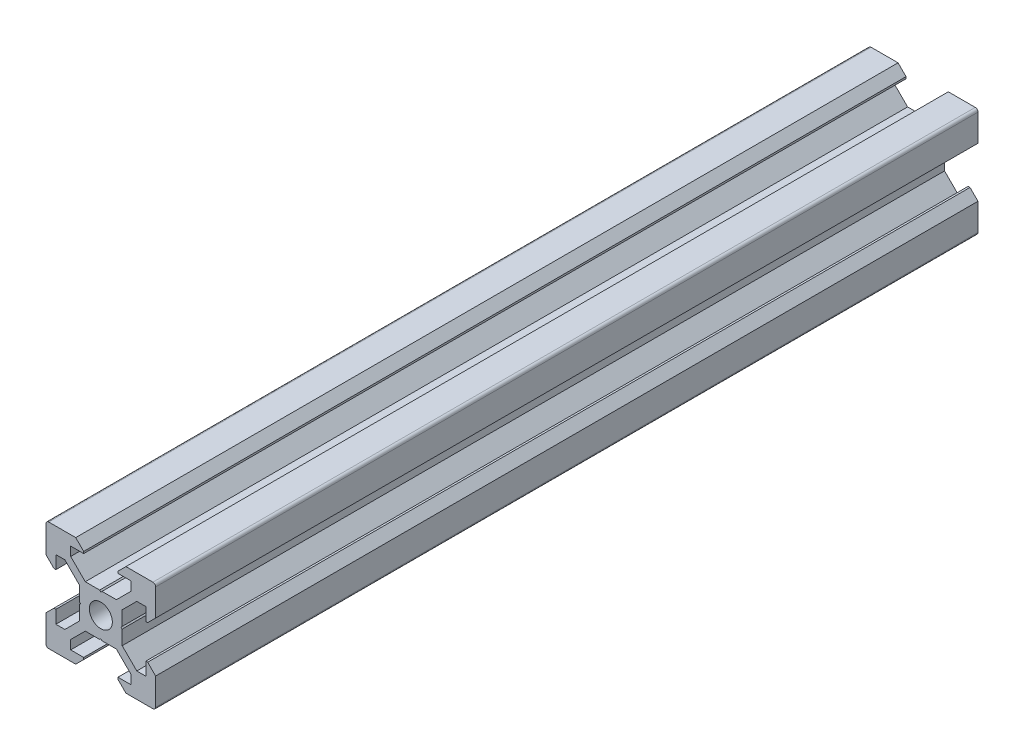
SolidWorks part; units mm, degrees
material "6061-T6 (SS)"
ref_plane "Front Plane" through (0, 0, 0) normal (0, 0, 1) x (1, 0, 0)
ref_plane "Top Plane" through (0, 0, 0) normal (0, 1, 0) x (1, 0, 0)
ref_plane "Right Plane" through (0, 0, 0) normal (1, 0, 0) x (0, 0, -1)
sketch "Sketch1" plane through (0, 0, 0) normal (0, 0, 1) x (1, 0, 0)
  line L1 (9.5, -10) -> (-9.5, -10)
  line L2 (10, -9.5) -> (10, 9.5)
  line L3 (9.5, 10) -> (-9.5, 10)
  line L4 (-10, -9.5) -> (-10, 9.5)
  line L5 (10, -10) -> (-10, 10) construction
  line L6 (10, 10) -> (-10, -10) construction
  circle A0 centre (0, 0) radius 2.1
  arc A1 (-9.5, 10) -> (-10, 9.5) centre (-9.5, 9.5) ccw
  arc A2 (10, 9.5) -> (9.5, 10) centre (9.5, 9.5) ccw
  arc A3 (9.5, -10) -> (10, -9.5) centre (9.5, -9.5) ccw
  arc A4 (-9.5, -10) -> (-10, -9.5) centre (-9.5, -9.5) cw
  point P0 (0, 0)
  line B0 (0, 0) -> (0, 10) construction
  line B1 (0, 3.69) -> (-0.21, 3.9)
  line B2 (-0.21, 3.9) -> (-2.8393, 3.9)
  line B3 (-2.8393, 3.9) -> (-5.5, 6.5607)
  line B4 (-5.5, 6.5607) -> (-5.5, 8.2)
  line B5 (-5.5, 8.2) -> (-3.125, 8.2)
  line B6 (-3.125, 8.2) -> (-3.125, 8.545)
  line B7 (-3.125, 8.545) -> (-4.58, 10)
  line B8 (-4.58, 10) -> (4.58, 10)
  line B9 (0, 0) -> (-5.9132, 5.9132) construction
  line B10 (3.125, 8.545) -> (4.58, 10)
  line B11 (3.125, 8.2) -> (3.125, 8.545)
  line B12 (5.5, 8.2) -> (3.125, 8.2)
  line B13 (5.5, 6.5607) -> (5.5, 8.2)
  line B14 (2.8393, 3.9) -> (5.5, 6.5607)
  line B15 (0.21, 3.9) -> (2.8393, 3.9)
  line B16 (0, 3.69) -> (0.21, 3.9)
  line B17 (0, 0) -> (-10, 0) construction
  line B18 (-3.69, 0) -> (-3.9, -0.21)
  line B19 (-3.9, -0.21) -> (-3.9, -2.8393)
  line B20 (-3.9, -2.8393) -> (-6.5607, -5.5)
  line B21 (-6.5607, -5.5) -> (-8.2, -5.5)
  line B22 (-8.2, -5.5) -> (-8.2, -3.125)
  line B23 (-8.2, -3.125) -> (-8.545, -3.125)
  line B24 (-8.545, -3.125) -> (-10, -4.58)
  line B25 (-10, -4.58) -> (-10, 4.58)
  line B26 (0, 0) -> (-5.9132, -5.9132) construction
  line B27 (-8.545, 3.125) -> (-10, 4.58)
  line B28 (-8.2, 3.125) -> (-8.545, 3.125)
  line B29 (-8.2, 5.5) -> (-8.2, 3.125)
  line B30 (-6.5607, 5.5) -> (-8.2, 5.5)
  line B31 (-3.9, 2.8393) -> (-6.5607, 5.5)
  line B32 (-3.9, 0.21) -> (-3.9, 2.8393)
  line B33 (-3.69, 0) -> (-3.9, 0.21)
  line B34 (0, 0) -> (0, -10) construction
  line B35 (0, -3.69) -> (0.21, -3.9)
  line B36 (0.21, -3.9) -> (2.8393, -3.9)
  line B37 (2.8393, -3.9) -> (5.5, -6.5607)
  line B38 (5.5, -6.5607) -> (5.5, -8.2)
  line B39 (5.5, -8.2) -> (3.125, -8.2)
  line B40 (3.125, -8.2) -> (3.125, -8.545)
  line B41 (3.125, -8.545) -> (4.58, -10)
  line B42 (4.58, -10) -> (-4.58, -10)
  line B43 (0, 0) -> (5.9132, -5.9132) construction
  line B44 (-3.125, -8.545) -> (-4.58, -10)
  line B45 (-3.125, -8.2) -> (-3.125, -8.545)
  line B46 (-5.5, -8.2) -> (-3.125, -8.2)
  line B47 (-5.5, -6.5607) -> (-5.5, -8.2)
  line B48 (-2.8393, -3.9) -> (-5.5, -6.5607)
  line B49 (-0.21, -3.9) -> (-2.8393, -3.9)
  line B50 (0, -3.69) -> (-0.21, -3.9)
  line B51 (0, 0) -> (10, 0) construction
  line B52 (3.69, 0) -> (3.9, 0.21)
  line B53 (3.9, 0.21) -> (3.9, 2.8393)
  line B54 (3.9, 2.8393) -> (6.5607, 5.5)
  line B55 (6.5607, 5.5) -> (8.2, 5.5)
  line B56 (8.2, 5.5) -> (8.2, 3.125)
  line B57 (8.2, 3.125) -> (8.545, 3.125)
  line B58 (8.545, 3.125) -> (10, 4.58)
  line B59 (10, 4.58) -> (10, -4.58)
  line B60 (0, 0) -> (5.9132, 5.9132) construction
  line B61 (8.545, -3.125) -> (10, -4.58)
  line B62 (8.2, -3.125) -> (8.545, -3.125)
  line B63 (8.2, -5.5) -> (8.2, -3.125)
  line B64 (6.5607, -5.5) -> (8.2, -5.5)
  line B65 (3.9, -2.8393) -> (6.5607, -5.5)
  line B66 (3.9, -0.21) -> (3.9, -2.8393)
  line B67 (3.69, 0) -> (3.9, -0.21)
  dimension "D1" = 4.2
  dimension "D3" = 0.5
  dimension "D2" = 20
sketch_block_instance "V Slot 1-4"
sketch_block "V Slot 1" parameters "D1"=10, "D2"=11, "D3"=4.3, "D4"=1.8, "D5"=0.21, "D6"=45, "D7"=9.16, "D8"=1.5, "D9"=6.25
sketch_block_instance "V Slot 1-5"
sketch_block_instance "V Slot 1-6"
sketch_block_instance "V Slot 1-7"
extrude "Boss-Extrude1" add sketch "Sketch1" along normal blind 150 contours B67 B52 B53 B54 B55 B56 B57 B58 L2 A2 L3 B10 B11 B12 B13 B14 B15 B16 B1 B2 B3 B4 B5 B6 B7 A1 L4 B27 B28 B29 B30 B31 B32 B33 B18 B19 B20 B21 B22 B23 B24 A4 L1 B44 B45 B46 B47 B48 B49 region at (7.04, -9.7172, 0)
